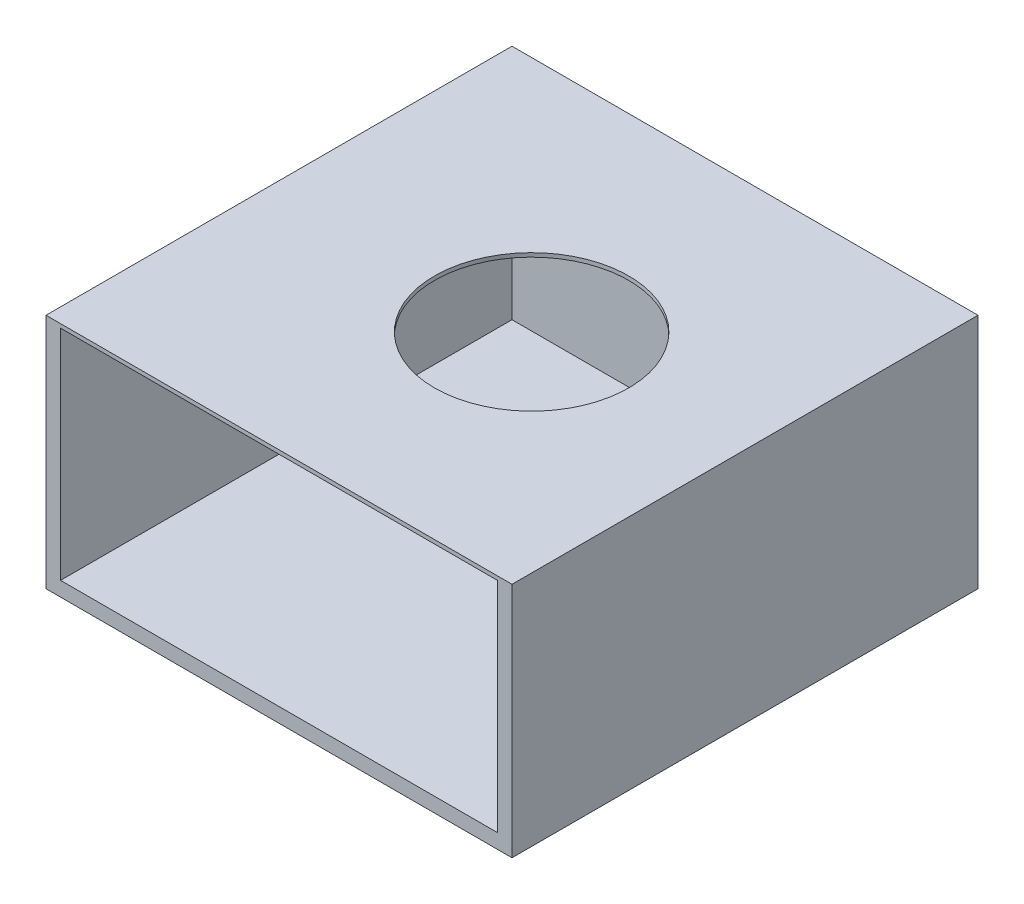
SolidWorks part; units mm, degrees
ref_plane "Front Plane" through (0, 0, 0) normal (0, 0, 1) x (1, 0, 0)
ref_plane "Top Plane" through (0, 0, 0) normal (0, 1, 0) x (1, 0, 0)
ref_plane "Right Plane" through (0, 0, 0) normal (1, 0, 0) x (0, 0, -1)
sketch "Sketch1" plane through (0, 0, 0) normal (0, 0, 1) x (1, 0, 0)
  line L1 (-152.4, -76.2) -> (152.4, -76.2)
  line L2 (-152.4, -76.2) -> (-152.4, 76.2)
  line L3 (-152.4, 76.2) -> (152.4, 76.2)
  line L4 (152.4, -76.2) -> (152.4, 76.2)
  line L5 (-152.4, -76.2) -> (152.4, 76.2) construction
  line L6 (-152.4, 76.2) -> (152.4, -76.2) construction
  point P0 (0, 0)
  dimension "D1" = 304.8
  dimension "D2" = 152.4
extrude "Boss-Extrude1" add sketch "Sketch1" along normal blind 304.8
shell "Shell1" thickness 9.525 removed face at (0, 0, 304.8) removed face at (0, 76.2, 152.4)
sketch "Sketch2" plane through (0, 76.2, 0) normal (0, 1, 0) x (1, 0, 0)
  line L0 (-142.875, -304.8) -> (142.875, -304.8)
  line L8 (-152.4, -304.8) -> (-142.875, -304.8)
  line L9 (-142.875, -304.8) -> (-142.875, -9.525)
  line L10 (-142.875, -9.525) -> (142.875, -9.525)
  line L11 (142.875, -9.525) -> (142.875, -304.8)
  line L12 (142.875, -304.8) -> (152.4, -304.8)
  line L13 (152.4, -304.8) -> (152.4, 0)
  line L14 (152.4, 0) -> (-152.4, 0)
  line L15 (-152.4, 0) -> (-152.4, -304.8)
  line L16 (-152.4, -304.8) -> (-142.875, -304.8)
  line L20 (142.875, -304.8) -> (152.4, -304.8)
  line L21 (152.4, -304.8) -> (152.4, 0)
  line L22 (152.4, 0) -> (-152.4, 0)
  line L23 (-152.4, 0) -> (-152.4, -304.8)
  dimension "D1" = 0
extrude "Boss-Extrude2" add sketch "Sketch2" along normal blind 2.54
sketch "Sketch3" plane through (0, 78.74, 0) normal (0, 1, 0) x (1, 0, 0)
  line L10 (15.875, -108.3347) -> (-28.9142, -140.876)
  line L11 (-28.9142, -140.876) -> (-11.8063, -193.5289)
  line L12 (-11.8063, -193.5289) -> (43.5563, -193.5289)
  line L13 (43.5563, -193.5289) -> (60.6642, -140.876)
  line L14 (60.6642, -140.876) -> (15.875, -108.3347)
  circle A1 centre (15.875, -155.4289) radius 3.175
sketch "Sketch4" plane through (0, 78.74, 0) normal (0, 1, 0) x (1, 0, 0)
  circle A0 centre (15.875, -155.4289) radius 63.5
  dimension "D1" = 127
extrude "Cut-Extrude1" cut sketch "Sketch4" against normal blind 7.62
